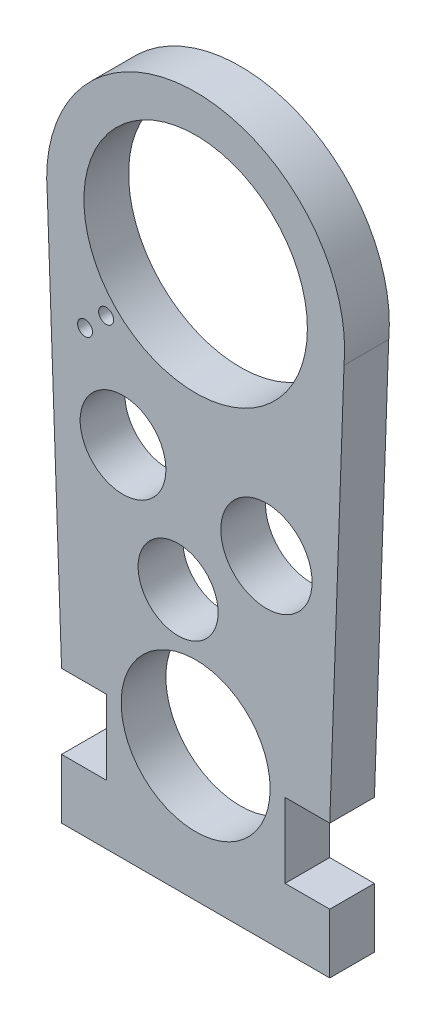
SolidWorks part; units mm, degrees
ref_plane "Plan de face" through (0, 0, 0) normal (0, 0, 1) x (1, 0, 0)
ref_plane "Plan de dessus" through (0, 0, 0) normal (0, 1, 0) x (1, 0, 0)
ref_plane "Plan de droite" through (0, 0, 0) normal (1, 0, 0) x (0, 0, -1)
sketch "Esquisse1" plane through (0, 0, 0) normal (0, 0, 1) x (1, 0, 0)
  line L0 (8.3168, 9) -> (0, 9) construction
  line L1 (0, 9) -> (0, 6) construction
  line L2 (0, 6) -> (8.0445, 6) construction
  line L3 (0, 0) -> (0, 28) construction
  line L4 (-7.5, 0) -> (-9.9591, 27.0962) construction
  line L5 (9.9591, 27.0962) -> (7.5, 0) construction
  line L6 (9.9591, 27.0962) -> (8.3168, 9) construction
  line L7 (8.0445, 6) -> (7.5, 0) construction
  line L8 (0, 0) -> (18.0723, 0) construction
  line L9 (7.5, 0) -> (6.6832, -9) construction
  line L12 (6.6832, -9) -> (0, -9) construction
  line L13 (0, -9) -> (0, -6) construction
  line L14 (0, -6) -> (-6.9555, -6) construction
  line L15 (-6.9555, -6) -> (-7.5, 0) construction
  line L16 (6, -6.7082) -> (6, 0) construction
  line L17 (6, 0) -> (9, 0)
  line L18 (9, 0) -> (9.9591, 27.0962)
  line L20 (-9, 0) -> (-9.9591, 27.0962)
  line L22 (-6, -6.7082) -> (-6, 0) construction
  line L23 (-6, 0) -> (-9, 0)
  line L24 (-7.4246, 20.5754) -> (0, 28) construction
  line L25 (6, 0) -> (6, -5)
  line L26 (6, -5) -> (9, -5)
  line L27 (9, -5) -> (9, -9)
  line L28 (9, -9) -> (-9, -9)
  line L29 (-9, -9) -> (-9, -5)
  line L30 (-9, -5) -> (-6, -5)
  line L31 (-6, -5) -> (-6, 0)
  circle A0 centre (0, 0) radius 5
  circle A1 centre (0, 28) radius 10 construction
  arc A2 (-9.9591, 27.0962) -> (9.9591, 27.0962) centre (0, 28) cw
  arc A4 (9, 0) -> (-9, 0) centre (0, 0) cw construction
  arc A5 (-6, -6.7082) -> (6, -6.7082) centre (0, 0) ccw construction
  circle A6 centre (-4.8742, 15.0481) radius 2.8775
  circle A7 centre (4.7507, 13.4162) radius 3.0635
  circle A8 centre (-1.1774, 8.4871) radius 2.6843
  circle A9 centre (-7.4246, 20.5754) radius 0.5
  circle A10 centre (-6.0104, 21.9896) radius 0.5
  circle A11 centre (0, 28) radius 9 construction
  circle A12 centre (0, 36.5) radius 0.5 construction
  circle A13 centre (0, 28) radius 7.5
  point P41 (0, 0)
  point P47 (0, 0)
  dimension "D1" = 10
  dimension "D4" = 10
  dimension "D13" = 1
  dimension "D14" = 1
  dimension "D17" = 15
  dimension "D2" = 3
  dimension "D3" = 9
  dimension "D7" = 28
  dimension "D5" = 15
  dimension "D6" = 15
  dimension "D8" = 9
  dimension "D9" = 3
  dimension "D10" = 3
  dimension "D12" = 6
  dimension "D11" = 1
  dimension "D15" = 45
  dimension "D16" = 27.1131
  dimension "D18" = 5
extrude "Boss.-Extru.1" add sketch "Esquisse1" along normal blind 3
equation "\"D8@Esquisse1\"=\"D3@Esquisse1\""
equation "\"D9@Esquisse1\"=\"D2@Esquisse1\""
